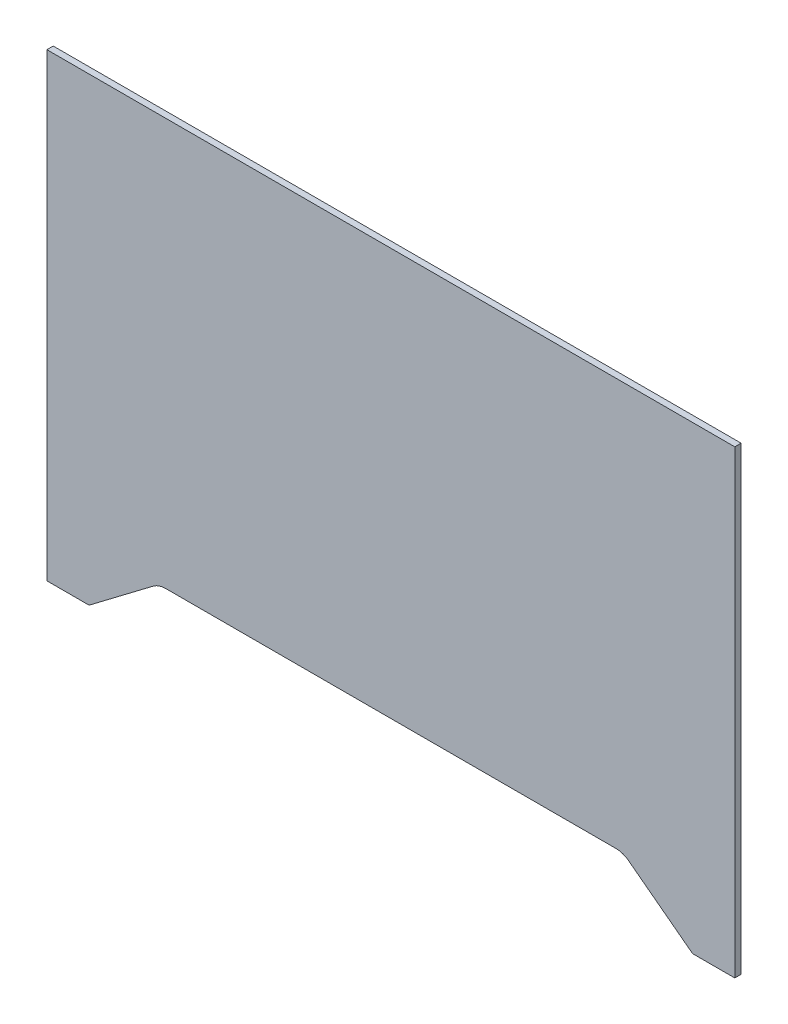
SolidWorks part; units mm, degrees
ref_plane "前视基准面" through (0, 0, 0) normal (0, 0, 1) x (1, 0, 0)
ref_plane "上视基准面" through (0, 0, 0) normal (0, 1, 0) x (1, 0, 0)
ref_plane "右视基准面" through (0, 0, 0) normal (1, 0, 0) x (0, 0, -1)
sketch "Sketch1" plane through (0, 0, 0) normal (0, 0, 1) x (1, 0, 0)
  line L0 (0, -109) -> (0, 0) construction
  line L1 (-163, -109) -> (163, -109) construction
  line L2 (-163, -109) -> (-163, 109)
  line L3 (-163, 109) -> (163, 109)
  line L4 (163, -109) -> (163, 109)
  line L5 (-163, -109) -> (163, 109) construction
  line L6 (-163, 109) -> (163, -109) construction
  line L7 (-106.6398, -84) -> (106.6398, -84)
  line L8 (112.6784, -86.0291) -> (143, -109)
  line L9 (143, -109) -> (163, -109)
  line L10 (-143, -109) -> (-163, -109)
  line L11 (-112.6784, -86.0291) -> (-143, -109)
  arc A0 (112.6784, -86.0291) -> (106.6398, -84) centre (106.6398, -94) ccw
  arc A1 (-112.6784, -86.0291) -> (-106.6398, -84) centre (-106.6398, -94) cw
  point P0 (0, 0)
  point P13 (110, -84)
  point P18 (0, -84)
  dimension "D6" = 10
  dimension "D1" = 326
  dimension "D2" = 218
  dimension "D3" = 25
  dimension "D4" = 20
  dimension "D5" = 110
extrude "Boss-Extrude1" add sketch "Sketch1" along normal blind 3
